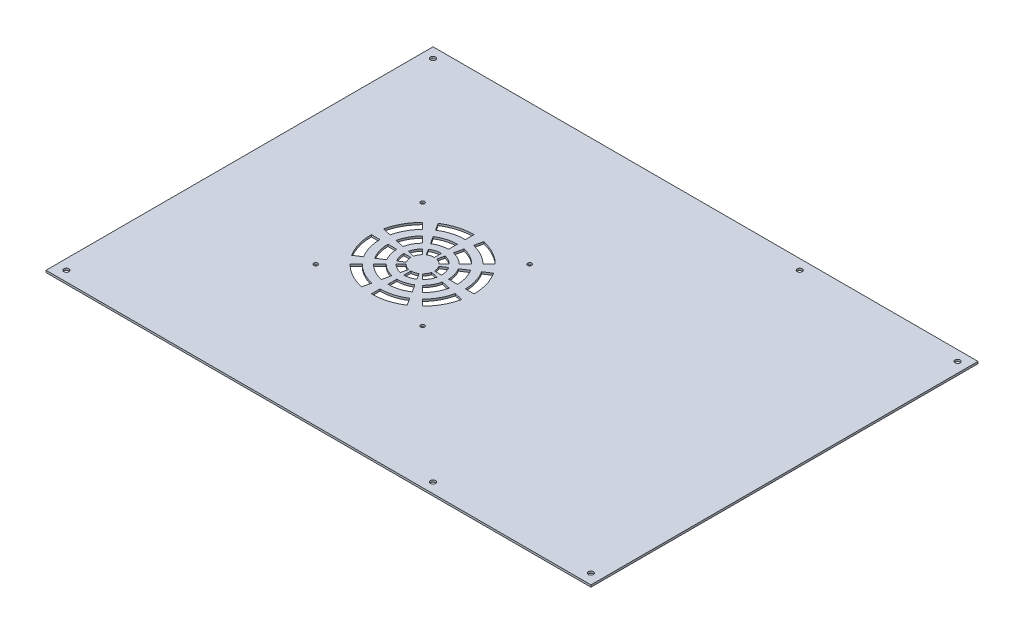
SolidWorks part; units mm, degrees
material "3.1645 (EN AW-2007)"
ref_plane "Přední rovina" through (0, 0, 0) normal (0, 0, 1) x (1, 0, 0)
ref_plane "Horní rovina" through (0, 0, 0) normal (0, 1, 0) x (1, 0, 0)
ref_plane "Pravá rovina" through (0, 0, 0) normal (1, 0, 0) x (0, 0, -1)
sketch "Skica1" plane through (0, 0, 0) normal (0, 1, 0) x (1, 0, 0)
  line L1 (267.5, -190) -> (-267.5, -190)
  line L2 (267.5, -190) -> (267.5, 190)
  line L3 (267.5, 190) -> (-267.5, 190)
  line L4 (-267.5, -190) -> (-267.5, 190)
  line L5 (267.5, -190) -> (-267.5, 190) construction
  line L6 (267.5, 190) -> (-267.5, -190) construction
  circle A0 centre (-257.5293, 180) radius 2.5
  circle A1 centre (-257.5, -180) radius 2.5
  circle A2 centre (102.5, -180) radius 2.5
  circle A3 centre (257.5, -180) radius 2.5
  circle A4 centre (102.5, 180) radius 2.5
  circle A5 centre (257.5, 180) radius 2.5
  point P0 (0, 0)
  dimension "D5" = 5
  dimension "D1" = 535
  dimension "D2" = 380
  dimension "D3" = 9.9707
  dimension "D4" = 10
  dimension "D6" = 10
  dimension "D7" = 10
  dimension "D8" = 10
  dimension "D9" = 10
  dimension "D10" = 10
  dimension "D11" = 155
  dimension "D12" = 155
  dimension "D13" = 10
  dimension "D14" = 10
  dimension "D15" = 10
extrude "Přidat vysunutím1" add sketch "Skica1" along normal blind 2
sketch "Skica2" plane through (0, 2, 0) normal (0, 1, 0) x (1, 0, 0)
  line L0 (-87.7064, 0) -> (0, 0) construction
  line L1 (-35.2064, 52.5) -> (-140.2064, 52.5) construction
  line L2 (-35.2064, 52.5) -> (-35.2064, -52.5) construction
  line L3 (-35.2064, -52.5) -> (-140.2064, -52.5) construction
  line L4 (-140.2064, 52.5) -> (-140.2064, -52.5) construction
  line L5 (-35.2064, 52.5) -> (-140.2064, -52.5) construction
  line L6 (-35.2064, -52.5) -> (-140.2064, 52.5) construction
  line L7 (-87.7064, 0) -> (-37.2871, 0)
  line L8 (-38.4486, -10.7599) -> (-87.7064, 0)
  line L9 (-60.4843, -42.4389) -> (-87.7064, 0)
  line L10 (-87.7064, 0) -> (-52.0546, -35.6518)
  line L11 (-98.4663, -49.2577) -> (-87.7064, 0)
  line L12 (-87.7064, 0) -> (-87.7064, -50.4192)
  line L13 (-130.1452, -27.2221) -> (-87.7064, 0)
  line L14 (-87.7064, 0) -> (-123.3581, -35.6518)
  line L15 (-136.9641, 10.7599) -> (-87.7064, 0)
  line L16 (-87.7064, 0) -> (-138.1256, 0)
  line L17 (-114.9284, 42.4389) -> (-87.7064, 0)
  line L18 (-87.7064, 0) -> (-123.3581, 35.6518)
  line L19 (-76.9465, 49.2577) -> (-87.7064, 0)
  line L20 (-87.7064, 0) -> (-87.7064, 50.4192)
  line L21 (-45.2675, 27.2221) -> (-87.7064, 0)
  line L22 (-87.7064, 0) -> (-52.0546, 35.6518)
  circle A0 centre (-140.2064, 52.5) radius 2
  circle A1 centre (-35.2064, 52.5) radius 2
  circle A2 centre (-140.2064, -52.5) radius 2
  circle A3 centre (-35.2064, -52.5) radius 2
  circle A4 centre (-87.7064, 0) radius 50.4192
  circle A5 centre (-87.7064, 0) radius 41.9096
  circle A6 centre (-87.7064, 0) radius 34.1039
  circle A7 centre (-87.7064, 0) radius 25.347
  circle A8 centre (-87.7064, 0) radius 18.4631
  circle A9 centre (-87.7064, 0) radius 11.5206
  point P0 (-87.7064, 0)
  point P36 (-87.7064, 0)
  dimension "D3" = 4
  dimension "D1" = 105
  dimension "D2" = 105
  dimension "D4" = 8
extrude "Odebrat vysunutím1" cut sketch "Skica2" against normal blind 2 contours A2 | A5 L12 A4 L9 | A5 L10 A4 L8 | A5 L7 A4 L21 | A5 L22 A4 L19 | A5 L20 A4 L17 | A5 L18 A4 L15 | A5 L16 A4 L13 | A5 L14 A4 L11 | A7 L14 A6 L11 | A7 L16 A6 L13 | A7 L18 A6 L15 | A7 L20 A6 L17 | A7 L22 A6 L19 | A7 L7 A6 L21 | A7 L10 A6 L8 | A7 L12 A6 L9 | A9 L14 A8 L11 | A9 L16 A8 L13 | A9 L18 A8 L15 | A9 L20 A8 L17 | A9 L22 A8 L19 | A9 L7 A8 L21 | A9 L10 A8 L8 | A9 L12 A8 L9 | A0 | A1 | A3 region at (-73.2605, 2, -4.2349) region at (-74.4971, 2, 7.2202) region at (-83.4715, 2, 14.4458) region at (-94.9266, 2, 13.2093) region at (-102.1522, 2, 4.2349) region at (-100.9156, 2, -7.2202) region at (-91.9413, 2, -14.4458) region at (-80.4861, 2, -13.2093) region at (-59.3629, 2, -8.3091) region at (-61.7891, 2, 14.1664) region at (-79.3973, 2, 28.3434) region at (-101.8728, 2, 25.9173) region at (-116.0498, 2, 8.3091) region at (-113.6236, 2, -14.1664) region at (-96.0155, 2, -28.3434) region at (-73.5399, 2, -25.9173) region at (-43.8806, 2, -12.8479) region at (-47.632, 2, 21.9047) region at (-74.8585, 2, 43.8258) region at (-109.6111, 2, 40.0743) region at (-131.5322, 2, 12.8479) region at (-127.7807, 2, -21.9047) region at (-100.5542, 2, -43.8258) region at (-65.8017, 2, -40.0743) region at (-140.2064, 2, 52.5)
